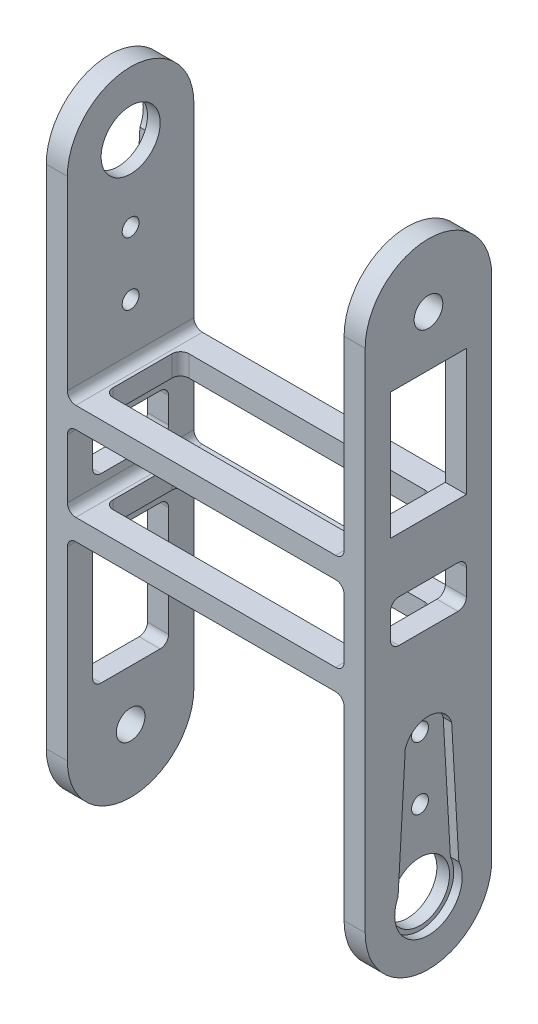
SolidWorks part; units mm, degrees
ref_plane "前视基准面" through (0, 0, 0) normal (0, 0, 1) x (1, 0, 0)
ref_plane "上视基准面" through (0, 0, 0) normal (0, 1, 0) x (1, 0, 0)
ref_plane "右视基准面" through (0, 0, 0) normal (1, 0, 0) x (0, 0, -1)
sketch "草图1" plane through (0, 0, 0) normal (0, 1, 0) x (1, 0, 0)
  line L0 (-16.5, 0) -> (16.5, 0) construction
  point P4 (0, 0)
  dimension "D1" = 33
ref_plane "基准面1" through (16.4, 0, 0) normal (1, 0, 0) x (0, 0, -1)
ref_plane "基准面2" through (-16.4, 0, 0) normal (-1, 0, 0) x (0, 0, 1)
sketch "草图4" plane through (-16.4, 0, 0) normal (-1, 0, 0) x (0, 0, 1)
  line L0 (0, 0) -> (0, -50000) construction
  line L1 (7.5, 60) -> (-7.5, 60) construction
  line L2 (-7.5, 60) -> (-7.5, 0)
  line L3 (-7.5, 0) -> (7.5, 0) construction
  line L4 (7.5, 0) -> (7.5, 60)
  circle A0 centre (0, 0) radius 7.5 construction
  circle A1 centre (0, 60) radius 7.5 construction
  arc A2 (7.5, 60) -> (-7.5, 60) centre (0, 60) ccw
  arc A3 (7.5, 0) -> (-7.5, 0) centre (0, 0) cw
  point P3 (0, 60)
  dimension "D1" = 15
  dimension "D2" = 60
  dimension "D3" = 15
sketch "草图5" plane through (16.4, 0, 0) normal (1, 0, 0) x (0, 0, -1)
  line L0 (7.5, 0) -> (-7.5, 0) construction
  line L1 (0, 0) -> (0, 29.9674) construction
  line L2 (-7.5, 60) -> (7.5, 60) construction
  line L3 (-7.5, 0) -> (-7.5, 60)
  line L4 (7.5, 60) -> (7.5, 0)
  circle A0 centre (0, 0) radius 7.5 construction
  circle A1 centre (0, 60) radius 7.5 construction
  arc A2 (-7.5, 0) -> (7.5, 0) centre (0, 0) ccw
  arc A3 (-7.5, 60) -> (7.5, 60) centre (0, 60) cw
  point P6 (0, 0)
  point P7 (0, 60)
  point P14 (0, 60)
  dimension "D1" = 15
  dimension "D2" = 60
  dimension "D3" = 15
extrude "凸台-拉伸1" add sketch "草图4" along normal blind 2.5
sketch "草图6" plane through (-18.9, 0, 0) normal (-1, 0, 0) x (0, 0, 1)
  circle A0 centre (0, 0) radius 1.7
  dimension "D1" = 3.4
extrude "切除-拉伸1" cut sketch "草图6" against normal blind 3
extrude "凸台-拉伸2" add sketch "草图5" along normal blind 2.5 separate body
sketch "草图7" plane through (18.9, 0, 0) normal (1, 0, 0) x (0, 0, -1)
  line L0 (0, 0) -> (0, 2.3395) construction
  line L1 (3.6, 1.7436) -> (-3.6, 1.7436) construction
  line L2 (-2.75, 16.5) -> (2.75, 16.5) construction
  line L3 (-3.6, 1.7436) -> (-2.75, 16.5)
  line L4 (3.6, 1.7436) -> (2.75, 16.5)
  circle A0 centre (0, 0) radius 4 construction
  arc A1 (-3.6, 1.7436) -> (3.6, 1.7436) centre (0, 0) ccw
  arc A2 (-2.75, 16.5) -> (2.75, 16.5) centre (0, 15.6094) cw
  point P4 (0, 18.5)
  point P6 (0, 16.5)
  point P10 (0, 1.7436)
  point P13 (0, 16.5)
  point P15 (0, -4)
  dimension "D1" = 8
  dimension "D2" = 22.5
  dimension "D3" = 2
  dimension "D4" = 7.2
  dimension "D5" = 5.5
extrude "切除-拉伸2" cut sketch "草图7" against normal blind 1
sketch "草图8" plane through (17.9, 0, 0) normal (1, 0, 0) x (0, 0, -1)
  line L0 (0, 0) -> (0, 50000) construction
  circle A0 centre (0, 0) radius 3.5
  circle A1 centre (0, 16.395) radius 1
  circle A2 centre (0, 8.955) radius 1
  point P6 (0, 16.395)
  point P7 (0, 8.955)
  dimension "D1" = 7
  dimension "D3" = 2
  dimension "D5" = 2
  dimension "D2" = 16.395
  dimension "D4" = 7.44
extrude "切除-拉伸3" cut sketch "草图8" against normal up to next (1.5 mm away)
sketch "草图9" plane through (18.9, 0, 0) normal (1, 0, 0) x (0, 0, -1)
  circle A0 centre (0, 60) radius 1.7
  arc A1 (7.5, 60) -> (-7.5, 60) centre (0, 60) ccw construction
  dimension "D1" = 3.4
extrude "切除-拉伸4" cut sketch "草图9" against normal up to next (2.5 mm away)
sketch "草图10" plane through (-18.9, 0, 0) normal (-1, 0, 0) x (0, 0, 1)
  line L0 (0, 69.716) -> (0, -49930.284) construction
  line L1 (3.6, 58.2564) -> (-3.6, 58.2564) construction
  line L2 (2.75, 43.5) -> (-2.75, 43.5) construction
  line L5 (-2.75, 43.5) -> (-3.6, 58.2564)
  line L6 (2.75, 43.5) -> (3.6, 58.2564)
  circle A0 centre (0, 60) radius 4 construction
  arc A1 (7.5, 60) -> (-7.5, 60) centre (0, 60) ccw construction
  arc A3 (3.6, 58.2564) -> (-3.6, 58.2564) centre (0, 60) ccw
  arc A4 (-2.75, 43.5) -> (2.75, 43.5) centre (0, 44.3906) ccw
  point P2 (0, 64)
  point P6 (0, 41.5)
  point P11 (0, 43.5)
  point P19 (0, 43.5)
  dimension "D1" = 8
  dimension "D2" = 22.5
  dimension "D3" = 2
  dimension "D4" = 7.2
  dimension "D5" = 5.5
extrude "切除-拉伸5" cut sketch "草图10" against normal blind 1
sketch "草图11" plane through (-17.9, 0, 0) normal (-1, 0, 0) x (0, 0, 1)
  line L0 (0, 70) -> (0, 62.0556) construction
  circle A0 centre (0, 60) radius 3.5
  arc A1 (3.6, 58.2564) -> (-3.6, 58.2564) centre (0, 60) ccw construction
  circle A2 centre (0, 43.605) radius 1
  circle A3 centre (0, 51.045) radius 1
  point P6 (0, 51.045)
  point P9 (0, 43.605)
  dimension "D1" = 7
  dimension "D4" = 2
  dimension "D5" = 2
  dimension "D2" = 16.395
  dimension "D3" = 7.44
extrude "切除-拉伸6" cut sketch "草图11" against normal up to next (1.5 mm away)
ref_axis "基准轴1" through (16.4, 60, 0) along (1, 0, 0)
ref_axis "基准轴2" through (-16.4, 0, 0) along (-1, 0, 0)
ref_plane "基准面6" through (0, 60, 0) normal (0, 1, 0) x (1, 0, 0)
ref_plane "基准面5" through (0, 30, 0) normal (0, 1, 0) x (1, 0, 0)
sketch "草图12" plane through (0, 0, 0) normal (0, 0, 1) x (1, 0, 0)
  line L0 (16.4, -8.25) -> (16.4, 8.25) construction
  line L1 (16.4, 37) -> (-16.4, 37) construction
  line L2 (16.4, 37) -> (16.4, 23) construction
  line L3 (16.4, 23) -> (-16.4, 23) construction
  line L4 (-16.4, 37) -> (-16.4, 23) construction
  line L5 (16.4, 37) -> (-16.4, 23) construction
  line L6 (16.4, 23) -> (-16.4, 37) construction
  line L7 (-16.4, 8.25) -> (-16.4, -8.25) construction
  line L11 (55, 30) -> (-55, 30) construction
  line L12 (16.4, 37) -> (-16.4, 37)
  line L13 (16.4, 37) -> (16.4, 34.5)
  line L14 (16.4, 34.5) -> (-16.4, 34.5)
  line L15 (-16.4, 37) -> (-16.4, 34.5)
  line L16 (16.4, 37) -> (-16.4, 34.5) construction
  line L17 (16.4, 34.5) -> (-16.4, 37) construction
  line L18 (16.4, 23) -> (-16.4, 23)
  line L19 (16.4, 23) -> (16.4, 25.5)
  line L20 (16.4, 25.5) -> (-16.4, 25.5)
  line L21 (-16.4, 23) -> (-16.4, 25.5)
  line L22 (16.4, 23) -> (-16.4, 25.5) construction
  line L23 (16.4, 25.5) -> (-16.4, 23) construction
  point P4 (0, 30)
  point P13 (0, 35.75)
  point P14 (0, 24.25)
  dimension "D2" = 14
  dimension "D3" = 2.5
  dimension "D4" = 2.5
extrude "凸台-拉伸3" add sketch "草图12" along normal up to surface and the other way up to surface up to face at (-17.65, 30, 7.5) other way up to face at (-17.65, 30, -7.5)
sketch "草图13" plane through (-18.9, 0, 0) normal (-1, 0, 0) x (0, 0, 1)
  line L0 (7.5, 0) -> (7.5, 60) construction
  line L1 (4.5, 21) -> (-4.5, 21)
  line L2 (4.5, 21) -> (4.5, 6)
  line L3 (4.5, 6) -> (-4.5, 6)
  line L4 (-4.5, 21) -> (-4.5, 6)
  line L5 (4.5, 21) -> (-4.5, 6) construction
  line L6 (4.5, 6) -> (-4.5, 21) construction
  line L7 (55, 30) -> (-55, 30) construction
  line L8 (4.5, 32.5) -> (-4.5, 32.5)
  line L9 (4.5, 32.5) -> (4.5, 27.5)
  line L10 (4.5, 27.5) -> (-4.5, 27.5)
  line L11 (-4.5, 32.5) -> (-4.5, 27.5)
  line L12 (4.5, 32.5) -> (-4.5, 27.5) construction
  line L13 (4.5, 27.5) -> (-4.5, 32.5) construction
  line L18 (7.5, 23) -> (-7.5, 23) construction
  line L19 (7.5, 25.5) -> (-7.5, 25.5) construction
  point P4 (0, 13.5)
  point P13 (0, 30)
  dimension "D1" = 7.5
  dimension "D2" = 9
  dimension "D3" = 6
  dimension "D4" = 2
  dimension "D5" = 9
  dimension "D6" = 7.5
  dimension "D7" = 2
extrude "切除-拉伸7" cut sketch "草图13" against normal up to surface (18.9 mm away) up to plane "右视基准面"
sketch "草图14" plane through (18.9, 0, 0) normal (1, 0, 0) x (0, 0, -1)
  line L0 (-7.5, 60) -> (-7.5, 0) construction
  line L1 (-4.5, 39) -> (4.5, 39)
  line L2 (-4.5, 39) -> (-4.5, 54)
  line L3 (-4.5, 54) -> (4.5, 54)
  line L4 (4.5, 39) -> (4.5, 54)
  line L5 (-4.5, 39) -> (4.5, 54) construction
  line L6 (-4.5, 54) -> (4.5, 39) construction
  line L7 (-4.5, 27.5) -> (4.5, 27.5)
  line L8 (-4.5, 27.5) -> (-4.5, 32.5)
  line L9 (-4.5, 32.5) -> (4.5, 32.5)
  line L10 (4.5, 27.5) -> (4.5, 32.5)
  line L11 (-4.5, 27.5) -> (4.5, 32.5) construction
  line L12 (-4.5, 32.5) -> (4.5, 27.5) construction
  line L13 (55, 30) -> (-55, 30) construction
  line L14 (-7.5, 37) -> (7.5, 37) construction
  line L15 (-7.5, 34.5) -> (7.5, 34.5) construction
  point P4 (0, 46.5)
  point P9 (0, 30)
  dimension "D1" = 6
  dimension "D2" = 2
  dimension "D3" = 9
  dimension "D4" = 7.5
  dimension "D5" = 7.5
  dimension "D6" = 9
  dimension "D7" = 2
extrude "切除-拉伸8" cut sketch "草图14" against normal up to next and the other way through all
sketch "草图15" plane through (0, 30, 0) normal (0, 1, 0) x (1, 0, 0)
  line L1 (-15, -4.5) -> (15, -4.5)
  line L2 (-15, -4.5) -> (-15, 4.5)
  line L3 (-15, 4.5) -> (15, 4.5)
  line L4 (15, -4.5) -> (15, 4.5)
  line L5 (-15, -4.5) -> (15, 4.5) construction
  line L6 (-15, 4.5) -> (15, -4.5) construction
  line L8 (16.4, 7.5) -> (-16.4, 7.5) construction
  point P4 (0, 0)
  dimension "D1" = 3
  dimension "D2" = 30
extrude "切除-拉伸9" cut sketch "草图15" against normal through all both and the other way through all
fillet "圆角1" radius 1 28 edges at (-16.4, 23, 0) (16.4, 23, 0) (16.4, 25.5, 0) (-16.4, 25.5, 0) (17.65, 27.5, -4.5) (17.65, 32.5, -4.5) (17.65, 32.5, 4.5) (17.65, 27.5, 4.5) (-17.65, 6, -4.5) (-17.65, 6, 4.5) (-17.65, 21, -4.5) (-17.65, 21, 4.5) (-15, 24.25, 4.5) (-15, 24.25, -4.5) (15, 24.25, -4.5) (15, 24.25, 4.5) (-17.65, 32.5, 4.5) (-17.65, 32.5, -4.5) (-17.65, 27.5, -4.5) (-17.65, 27.5, 4.5) (-16.4, 34.5, 0) (16.4, 34.5, 0) (15, 35.75, -4.5) (-15, 35.75, -4.5) (-15, 35.75, 4.5) (15, 35.75, 4.5) (16.4, 37, 0) (-16.4, 37, 0)
